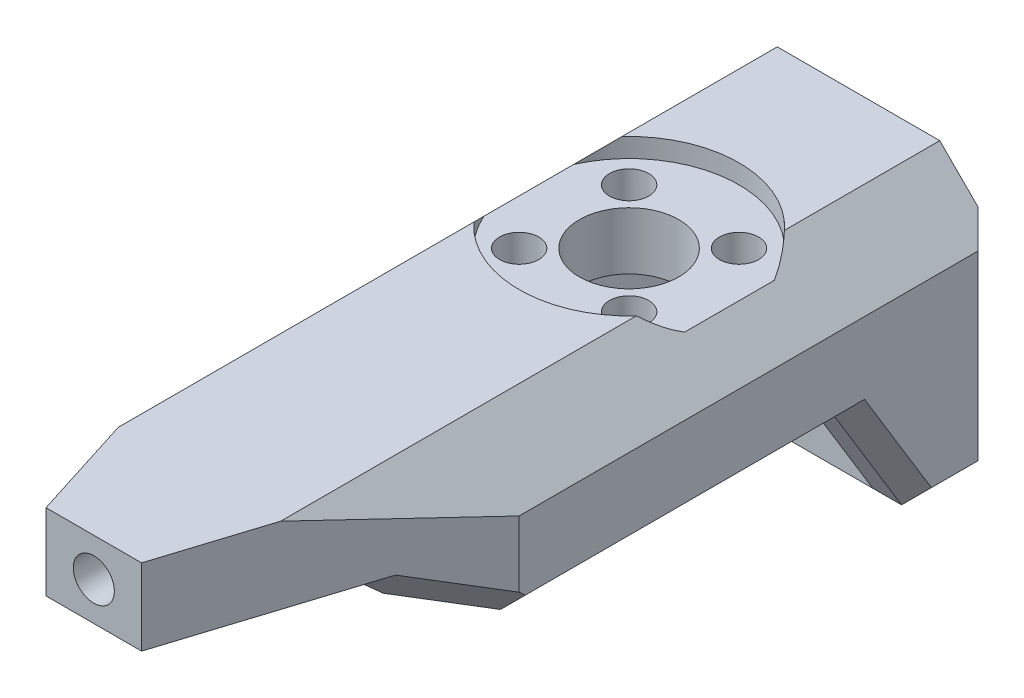
SolidWorks part; units mm, degrees
ref_plane "Front Plane" through (0, 0, 0) normal (0, 0, 1) x (1, 0, 0)
ref_plane "Top Plane" through (0, 0, 0) normal (0, 1, 0) x (1, 0, 0)
ref_plane "Right Plane" through (0, 0, 0) normal (1, 0, 0) x (0, 0, -1)
sketch "Sketch1" plane through (0, 0, 0) normal (0, 0, 1) x (1, 0, 0)
  line L1 (-13, 11.5) -> (13, 11.5)
  line L2 (-13, 11.5) -> (-13, -11.5)
  line L3 (-13, -11.5) -> (13, -11.5)
  line L4 (13, 11.5) -> (13, -11.5)
  line L5 (-13, 11.5) -> (13, -11.5) construction
  line L6 (-13, -11.5) -> (13, 11.5) construction
  circle A0 centre (-6, 4) radius 1.05
  circle A1 centre (6, 4) radius 1.05
  circle A2 centre (-6, -4) radius 1.05
  circle A3 centre (6, -4) radius 1.05
  point P0 (0, 0)
  point P14 (0, 0)
  point P15 (0, 0)
  point P16 (0, 0)
  point P17 (0, 0)
  dimension "D3" = 2.1
  dimension "D1" = 23
  dimension "D2" = 26
  dimension "D4" = 12
  dimension "D5" = 8
  dimension "D6" = 4
  dimension "D7" = 6
extrude "Boss-Extrude1" add sketch "Sketch1" along normal blind 8
sketch "Sketch2" plane through (0, 0, 8) normal (0, 0, 1) x (1, 0, 0)
  circle A0 centre (-6, 4) radius 3.55
  circle A1 centre (6, 4) radius 3.55
  circle A2 centre (6, -4) radius 3.55
  circle A3 centre (-6, -4) radius 3.55
  dimension "D1" = 7.1
extrude "Cut-Extrude1" cut sketch "Sketch2" against normal blind 1
sketch "Sketch3" plane through (0, 0, 8) normal (0, 0, 1) x (1, 0, 0)
  line L0 (13, -11.5) -> (13, 11.5) construction
  line L1 (-13, 11.5) -> (13, 11.5)
  line L2 (-13, 11.5) -> (-13, 7.5)
  line L3 (-9.5, 7.5) -> (9.5, 7.5)
  line L4 (13, 11.5) -> (13, 7.5)
  line L5 (-13, -11.5) -> (13, -11.5) construction
  line L7 (13, 7.5) -> (13, -11.5)
  line L8 (13, -11.5) -> (9.5, -11.5)
  line L9 (9.5, 7.5) -> (9.5, -11.5)
  line L11 (-13, -11.5) -> (-9.5, -11.5)
  line L12 (-13, -11.5) -> (-13, 7.5)
  line L14 (-9.5, -11.5) -> (-9.5, 7.5)
  dimension "D1" = 4
  dimension "D2" = 3.5
  dimension "D3" = 3.5
  dimension "D4" = 4
extrude "Boss-Extrude2" add sketch "Sketch3" along normal blind 72
sketch "Sketch4" plane through (-13, 0, 0) normal (-1, 0, 0) x (0, 0, 1)
  line L4 (0, 11.5) -> (0, -11.5)
  line L5 (0, -11.5) -> (80, -11.5)
  line L6 (80, -11.5) -> (80, 11.5)
  line L7 (80, 11.5) -> (0, 11.5)
  line L8 (0, 11.5) -> (0, -11.5)
  line L9 (0, -11.5) -> (80, -11.5)
  line L10 (80, -11.5) -> (80, 11.5)
  line L11 (80, 11.5) -> (0, 11.5)
  dimension "D1" = 0
extrude "Boss-Extrude3" add sketch "Sketch4" along normal blind 1.5
sketch "Sketch5" plane through (13, 0, 0) normal (1, 0, 0) x (0, 0, -1)
  line L4 (0, -11.5) -> (0, 11.5)
  line L5 (0, 11.5) -> (-80, 11.5)
  line L6 (-80, 11.5) -> (-80, -11.5)
  line L7 (-80, -11.5) -> (0, -11.5)
  line L8 (0, -11.5) -> (0, 11.5)
  line L9 (0, 11.5) -> (-80, 11.5)
  line L10 (-80, 11.5) -> (-80, -11.5)
  line L11 (-80, -11.5) -> (0, -11.5)
  dimension "D1" = 0
extrude "Boss-Extrude4" add sketch "Sketch5" along normal blind 1.5
sketch "Sketch6" plane through (0, 11.5, 0) normal (0, 1, 0) x (1, 0, 0)
  line L4 (14.5, 0) -> (-14.5, 0)
  line L5 (-14.5, 0) -> (-14.5, -80)
  line L6 (-14.5, -80) -> (14.5, -80)
  line L7 (14.5, -80) -> (14.5, 0)
  line L8 (14.5, 0) -> (-14.5, 0)
  line L9 (-14.5, 0) -> (-14.5, -80)
  line L10 (-14.5, -80) -> (14.5, -80)
  line L11 (14.5, -80) -> (14.5, 0)
  dimension "D1" = 0
extrude "Boss-Extrude5" add sketch "Sketch6" along normal blind 2
sketch "Sketch7" plane through (14.5, 0, 0) normal (1, 0, 0) x (0, 0, -1)
  line L0 (-8, -11.5) -> (-15, 0)
  line L1 (-80, -11.5) -> (0, -11.5) construction
  line L2 (-15, 0) -> (-52, 0)
  line L3 (-52, 0) -> (-80, 7.5)
  line L4 (-80, 13.5) -> (-80, -11.5) construction
  line L5 (-80, 7.5) -> (-80, -11.5)
  line L6 (-80, -11.5) -> (-8, -11.5)
  point P4 (-80, 3.5448)
  point P12 (-51.1025, 0)
  dimension "D1" = 8
  dimension "D2" = 15
  dimension "D3" = 6
  dimension "D4" = 28
extrude "Cut-Extrude2" cut sketch "Sketch7" against normal through all
sketch "Sketch8" plane through (-14.5, 0, 0) normal (-1, 0, 0) x (0, 0, 1)
  line L1 (80, 13.5) -> (50, 13.5)
  line L2 (80, 13.5) -> (80, 17.5)
  line L3 (80, 17.5) -> (50, 17.5)
  line L4 (50, 13.5) -> (50, 17.5)
  dimension "D1" = 10
  dimension "D2" = 30
extrude "Boss-Extrude6" add sketch "Sketch8" against normal up to surface (29 mm away) up to face at (14.5, 1.6429, 33.5714)
sketch "Sketch9" plane through (0, 17.5, 0) normal (0, 1, 0) x (1, 0, 0)
  line L0 (-5, -80) -> (-14.5, -50)
  line L1 (14.5, -80) -> (-14.5, -80) construction
  line L2 (-14.5, -50) -> (-14.5, -80)
  line L3 (-14.5, -80) -> (-5, -80)
  line L4 (14.5, -50) -> (14.5, -80)
  line L5 (14.5, -80) -> (5, -80)
  line L6 (5, -80) -> (14.5, -50)
  dimension "D1" = 10
  dimension "D2" = 9.5
extrude "Cut-Extrude3" cut sketch "Sketch9" against normal through all
sketch "Sketch10" plane through (14.5, 0, 0) normal (1, 0, 0) x (0, 0, -1)
  line L1 (-50, 0) -> (-65.7895, 0)
  line L2 (-50, 0) -> (-50, 7.5)
  line L3 (-50, 7.5) -> (-65.7895, 7.5)
  line L4 (-65.7895, 0) -> (-65.7895, 7.5)
extrude "Cut-Extrude4" cut sketch "Sketch10" against normal through all
chamfer "Chamfer1" distance 7.5 distance2 15 1 edges at (12, 7.5, 50) first distance on face at (12, 3.75, 50)
chamfer "Chamfer2" distance 7.5 distance2 15 1 edges at (-12, 7.5, 50) first distance on face at (-12, 3.75, 50)
chamfer "Chamfer3" distance 10 distance2 4 1 edges at (0, 13.5, 50) first distance on face at (0, 13.5, 25)
sketch "Sketch12" plane through (0, 13.5, 0) normal (0, 1, 0) x (1, 0, 0)
  circle A0 centre (0, -24) radius 5.2
  point P2 (0, -26.3877)
  point P4 (0, -24)
  dimension "D1" = 10.4
  dimension "D2" = 24
extrude "Cut-Extrude5" cut sketch "Sketch12" against normal through all
sketch "Sketch14" plane through (0, 13.5, 0) normal (0, 1, 0) x (1, 0, 0)
  circle A0 centre (5.75, -18.25) radius 2.05
  circle A1 centre (5.75, -29.75) radius 2.05
  circle A2 centre (-5.75, -29.75) radius 2.05
  circle A3 centre (-5.75, -18.25) radius 2.05
  circle A4 centre (0, -24) radius 5.2 construction
  point P8 (0, 0)
  point P9 (0, 0)
  point P10 (0, 0)
  point P11 (0, 0)
  dimension "D1" = 4.1
  dimension "D2" = 11.5
  dimension "D3" = 5.75
  dimension "D4" = 11.5
  dimension "D5" = 5.75
extrude "Cut-Extrude6" cut sketch "Sketch14" against normal blind 5
sketch "Sketch15" plane through (0, 0, 80) normal (0, 0, 1) x (1, 0, 0)
  circle A0 centre (0, 11.5) radius 2.15
  point P2 (0, 11.833)
  dimension "D1" = 4.3
  dimension "D2" = 4
extrude "Cut-Extrude8" cut sketch "Sketch15" against normal blind 22
sketch "Sketch21" plane through (0, 0, 80) normal (0, 0, 1) x (1, 0, 0)
  line L0 (14.5, 0) -> (14.5, 17.5) construction
  line L1 (-14.5, 17.5) -> (14.5, 17.5)
  line L2 (-14.5, 17.5) -> (-14.5, 15.5)
  line L3 (-14.5, 15.5) -> (14.5, 15.5)
  line L4 (14.5, 17.5) -> (14.5, 15.5)
  dimension "D1" = 2
extrude "Cut-Extrude9" cut sketch "Sketch21" against normal through all
sketch "Sketch22" plane through (0, 0, 0) normal (0, 0, -1) x (-1, 0, 0)
  line L1 (14.5, 13.5) -> (-14.5, 13.5)
  line L2 (14.5, 13.5) -> (14.5, 15.5)
  line L3 (14.5, 15.5) -> (-14.5, 15.5)
  line L4 (-14.5, 13.5) -> (-14.5, 15.5)
extrude "Boss-Extrude7" add sketch "Sketch22" against normal up to surface (40 mm away) up to face at (0, 14.5, 42.5)
sketch "Sketch23" plane through (0, 13.5, 0) normal (0, -1, 0) x (-1, 0, 0)
  circle A1 centre (0, -24) radius 5.2
  circle A2 centre (0, -24) radius 5.2
  dimension "D1" = 0
extrude "Cut-Extrude10" cut sketch "Sketch23" against normal through all
sketch "Sketch24" plane through (0, 15.5, 0) normal (0, 1, 0) x (1, 0, 0)
  circle A0 centre (0, -24) radius 11.5
  dimension "D1" = 23
extrude "Cut-Extrude11" cut sketch "Sketch24" against normal blind 2
chamfer "Chamfer4" distance 6 angle 45 2 edges at (-14.5, 15.5, 25) (14.5, 15.5, 25)
chamfer "Chamfer5" distance 2 angle 45 8 edges at (-12.125, 3.75, 57.5) (12.125, 3.75, 57.5) (14.5, 0, 32.5) (14.5, -5.75, 11.5) (14.5, -11.5, 4) (-14.5, -11.5, 4) (-14.5, -5.75, 11.5) (-14.5, 0, 32.5) first distance on face at (-10.8125, 3.75, 57.5) first distance on face at (10.8125, 3.75, 57.5) first distance on face at (12, 0, 32.5) first distance on face at (12, -5.75, 11.5) first distance on face at (0, -11.5, 5.3333) first distance on face at (-12, -5.75, 11.5) first distance on face at (-12, 0, 32.5)
chamfer "Chamfer6" distance 2 angle 45 2 edges at (14.5, 0, 0) (-14.5, 0, 0)
